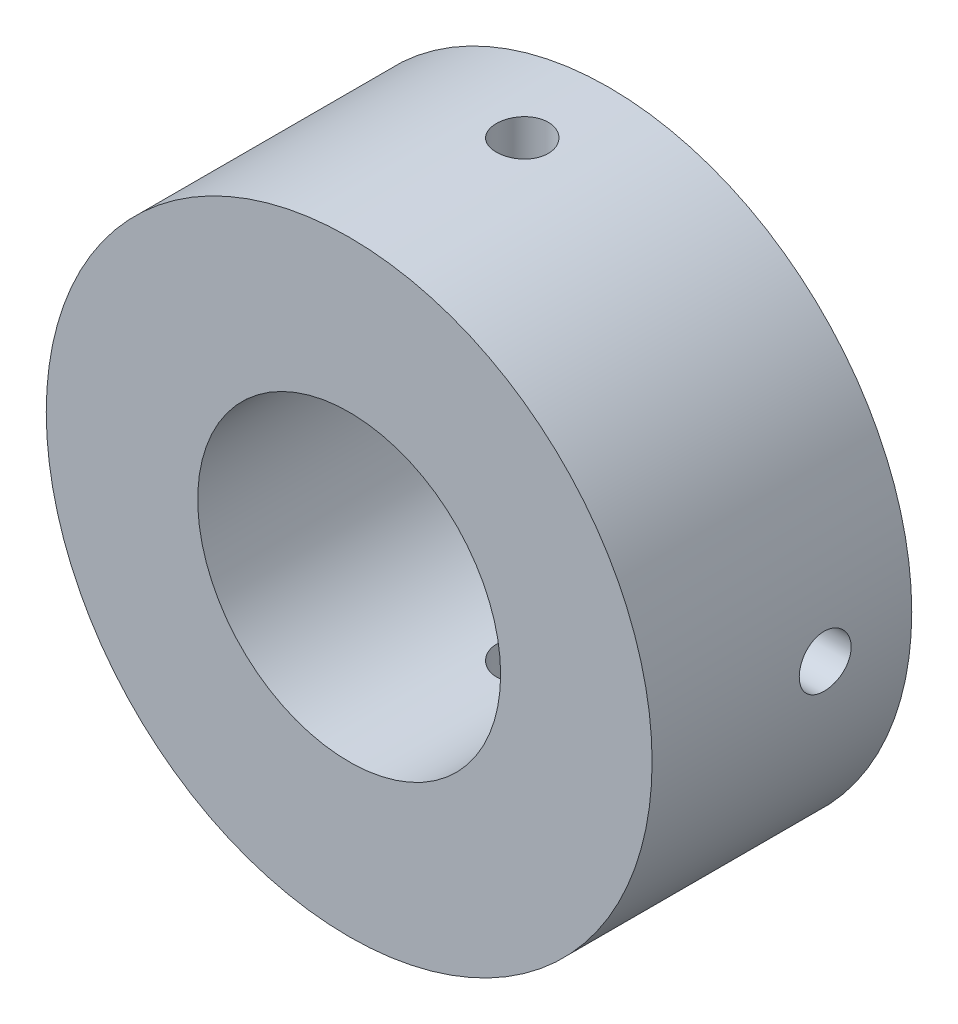
SolidWorks part; units mm, degrees
ref_plane "Front Plane" through (0, 0, 0) normal (0, 0, 1) x (1, 0, 0)
ref_plane "Top Plane" through (0, 0, 0) normal (0, 1, 0) x (1, 0, 0)
ref_plane "Right Plane" through (0, 0, 0) normal (1, 0, 0) x (0, 0, -1)
ref_axis "Z" through (0, 0, 10.75) along (0, 0, -1)
ref_axis "X" through (17.0818, 0, 0) along (-1, 0, 0)
ref_axis "Y" through (0, 19.25, 0) along (0, -1, 0)
sketch "Sketch1" plane through (0, 0, 0) normal (0, 0, 1) x (1, 0, 0)
  circle A0 centre (0, 0) radius 17.5
  circle A1 centre (0, 0) radius 8.75
  dimension "D1" = 35
  dimension "D2" = 17.5
extrude "Boss-Extrude1" add sketch "Sketch1" against normal blind 5 and the other way blind 10
sketch "Sketch2" plane through (0, 0, 0) normal (0, 1, 0) x (1, 0, 0)
  line L0 (-19.25, 0) -> (19.25, 0) construction
  line L1 (0, -8.25) -> (0, 8.25) construction
  circle A0 centre (0, 0) radius 1.5
  dimension "D1" = 3
extrude "Cut-Extrude1" cut sketch "Sketch2" against normal through all both and the other way through all
sketch "Sketch3" plane through (0, 0, 0) normal (1, 0, 0) x (0, 0, -1)
  circle A0 centre (0, 0) radius 1.5
  dimension "D1" = 3
extrude "Cut-Extrude2" cut sketch "Sketch3" along normal through all
equation "\"EyeDiameter\" = 35"
equation "\"BasePlaneDistance\" = \"EyeDiameter\"/2+19.84"
equation "\"EyeClearance\" = 2"
equation "\"EyeOD\"= \"EyeDiameter\""
equation "\"D1@Sketch1\"=\"EyeOD\""
equation "\"D2@Sketch1\"=\"EyeDiameter\"*0.5"
equation "\"pinHoleDiameter\"= 3"
equation "\"D1@Sketch2\"=\"pinHoleDiameter\""
equation "\"D1@Sketch3\"=\"pinHoleDiameter\""
